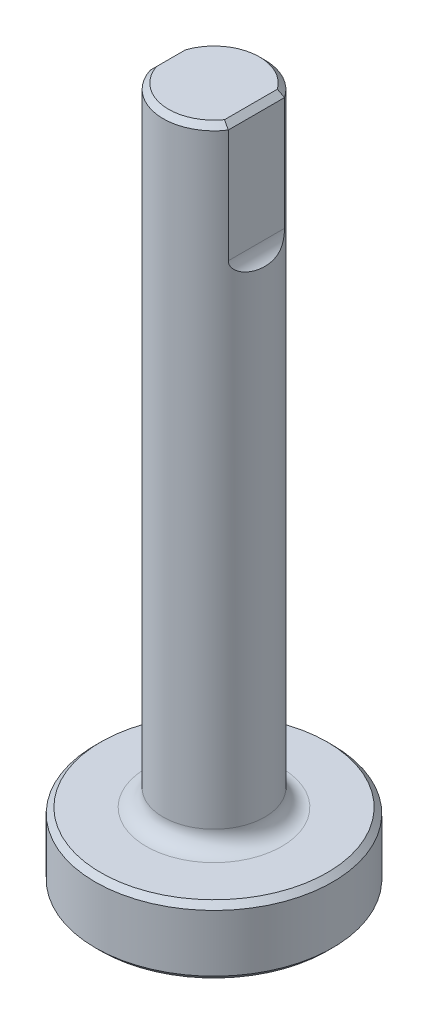
SolidWorks part; units mm, degrees
ref_plane "Front Plane" through (0, 0, 0) normal (0, 0, 1) x (1, 0, 0)
ref_plane "Top Plane" through (0, 0, 0) normal (0, 1, 0) x (1, 0, 0)
ref_plane "Right Plane" through (0, 0, 0) normal (1, 0, 0) x (0, 0, -1)
sketch "Sketch1" plane through (0, 0, 0) normal (0, 0, 1) x (1, 0, 0)
  line L0 (0, 3.4694) -> (0, -3.4694) construction
  line L1 (0, 0) -> (5.5562, 0)
  line L2 (5.5562, 0) -> (5.5562, 3.175)
  line L3 (5.5562, 3.175) -> (2.3812, 3.175)
  line L4 (2.3812, 3.175) -> (2.3813, 32.5437)
  line L5 (2.3813, 32.5437) -> (0, 32.5437)
  line L6 (0, 32.5437) -> (0, 0)
  dimension "D1" = 11.1125
  dimension "D2" = 4.7625
  dimension "D3" = 3.175
  dimension "D4" = 32.5437
revolve "Revolve1" add sketch "Sketch1" angle 360 about L0
sketch "Sketch4" plane through (0, 32.5437, 0) normal (0, 1, 0) x (1, 0, 0)
  line L0 (-2.2704, 0) -> (1.9844, 0) construction
  line L2 (-2.2704, -0.7181) -> (-2.2704, 0.7181)
  line L4 (1.9844, -1.3163) -> (1.9844, 1.3163)
  circle A0 centre (0, 0) radius 2.3812 construction
  arc A1 (1.9844, -1.3163) -> (1.9844, 1.3163) centre (0, 0) ccw
  arc A2 (-2.2704, 0.7181) -> (-2.2704, -0.7181) centre (0, 0) ccw
  point P0 (0, 0)
  dimension "D1" = 0.3969
extrude "Cut-Extrude1" cut sketch "Sketch4" against normal blind 6.35
fillet "Fillet1" radius 0.7937 1 edges at (0, 3.175, 2.3812)
fillet "Fillet2" radius 0.7937 2 edges at (1.9844, 26.1937, 0) (-2.2704, 26.1937, 0)
chamfer "Chamfer1" distance 0.254 angle 45 6 edges at (0, 0, 5.5562) (0, 3.175, 5.5562) (1.9844, 32.5437, 0) (-0.3315, 32.5437, 2.3581) (-2.2704, 32.5437, 0) (-0.3315, 32.5437, -2.3581)
